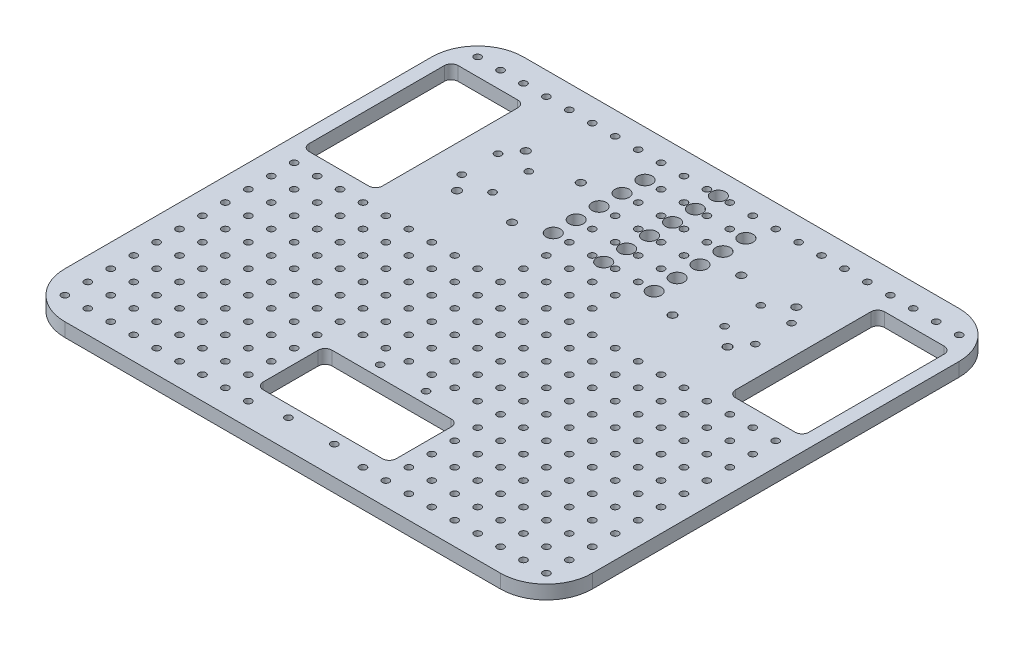
SolidWorks part; units mm, degrees
ref_plane "Спереди" through (0, 0, 0) normal (0, 0, 1) x (1, 0, 0)
ref_plane "Сверху" through (0, 0, 0) normal (0, 1, 0) x (1, 0, 0)
ref_plane "Справа" through (0, 0, 0) normal (1, 0, 0) x (0, 0, -1)
sketch "Эскиз1" plane through (0, 0, 0) normal (0, 1, 0) x (1, 0, 0)
  line L0 (94.4, 150) -> (0, 150) construction
  line L1 (0, 0) -> (230, 0)
  line L6 (115, 0) -> (115, 118.2603) construction
  line L10 (230, 0) -> (230, 200)
  line L28 (230, 200) -> (0, 200)
  line L29 (0, 200) -> (0, 0)
  circle A16 centre (80, 135) radius 1.73
  circle A19 centre (80, 165) radius 1.73
  circle A22 centre (56, 165) radius 1.73
  circle A23 centre (56, 135) radius 1.73
  circle A24 centre (150, 135) radius 1.73
  circle A25 centre (174, 135) radius 1.73
  circle A26 centre (150, 165) radius 1.73
  circle A27 centre (174, 165) radius 1.73
  point P7 (115, 25)
  dimension "D1" = 230
  dimension "D2" = 200
  dimension "D3" = 150
  dimension "D7" = 24
  dimension "D8" = 30
  dimension "D9" = 35
extrude "Бобышка-Вытянуть1" add sketch "Эскиз1" along normal blind 6
fillet "Скругление1" radius 20 4 edges at (0, 3, 0) (230, 3, 0) (230, 3, -200) (0, 3, -200)
sketch "Эскиз2" plane through (0, 6, 0) normal (0, 1, 0) x (1, 0, 0)
  line L0 (174, 165) -> (174, 135) construction
  line L1 (224, 182.5) -> (192, 182.5)
  line L2 (224, 182.5) -> (224, 117.5)
  line L3 (224, 117.5) -> (192, 117.5)
  line L4 (192, 182.5) -> (192, 117.5)
  line L5 (174, 150) -> (192, 150) construction
  line L6 (115, 200) -> (115, 0) construction
  line L7 (210, 200) -> (20, 200) construction
  line L8 (20, 0) -> (210, 0) construction
  line L9 (56, 150) -> (38, 150) construction
  line L10 (56, 165) -> (56, 135) construction
  line L11 (38, 182.5) -> (38, 117.5)
  line L12 (6, 117.5) -> (38, 117.5)
  line L13 (6, 182.5) -> (6, 117.5)
  line L14 (6, 182.5) -> (38, 182.5)
  line L15 (86, 32.5) -> (144, 32.5) construction
  line L16 (86, 47.5) -> (144, 47.5)
  line L17 (86, 47.5) -> (86, 17.5)
  line L18 (86, 17.5) -> (144, 17.5)
  line L19 (144, 47.5) -> (144, 17.5)
  circle A0 centre (105, 12.5) radius 1.5
  circle A1 centre (125, 12.5) radius 1.5
  circle A2 centre (105, 52.5) radius 1.5
  circle A3 centre (125, 52.5) radius 1.5
  dimension "D7" = 3
  dimension "D1" = 65
  dimension "D2" = 18
  dimension "D3" = 32
  dimension "D4" = 58
  dimension "D5" = 30
  dimension "D6" = 17.5
  dimension "D8" = 20
  dimension "D9" = 40
extrude "Вырез-Вытянуть1" cut sketch "Эскиз2" against normal blind 10
fillet "Скругление2" radius 3 12 edges at (224, 3, -117.5) (224, 3, -182.5) (192, 3, -182.5) (192, 3, -117.5) (6, 3, -117.5) (38, 3, -117.5) (38, 3, -182.5) (6, 3, -182.5) (86, 3, -17.5) (144, 3, -17.5) (144, 3, -47.5) (86, 3, -47.5)
sketch "Эскиз3" plane through (0, 6, 0) normal (0, 1, 0) x (1, 0, 0)
  line L0 (20, 0) -> (210, 0) construction
  line L1 (0, 180) -> (0, 20) construction
  line L2 (115, 190) -> (115, 200) construction
  line L3 (210, 200) -> (20, 200) construction
  circle A0 centre (10, 10) radius 1.5
  circle A1 centre (20, 10) radius 1.5
  circle A2 centre (30, 10) radius 1.5
  circle A3 centre (40, 10) radius 1.5
  circle A4 centre (50, 10) radius 1.5
  circle A5 centre (60, 10) radius 1.5
  circle A6 centre (70, 10) radius 1.5
  circle A7 centre (80, 10) radius 1.5
  circle A8 centre (90, 10) radius 1.5
  circle A13 centre (140, 10) radius 1.5
  circle A14 centre (150, 10) radius 1.5
  circle A15 centre (160, 10) radius 1.5
  circle A16 centre (170, 10) radius 1.5
  circle A17 centre (180, 10) radius 1.5
  circle A18 centre (190, 10) radius 1.5
  circle A19 centre (200, 10) radius 1.5
  circle A20 centre (210, 10) radius 1.5
  circle A21 centre (220, 10) radius 1.5
  circle A22 centre (20, 20) radius 1.5
  circle A23 centre (30, 20) radius 1.5
  circle A24 centre (40, 20) radius 1.5
  circle A25 centre (50, 20) radius 1.5
  circle A26 centre (60, 20) radius 1.5
  circle A27 centre (70, 20) radius 1.5
  circle A28 centre (80, 20) radius 1.5
  circle A35 centre (150, 20) radius 1.5
  circle A36 centre (160, 20) radius 1.5
  circle A37 centre (170, 20) radius 1.5
  circle A38 centre (180, 20) radius 1.5
  circle A39 centre (190, 20) radius 1.5
  circle A40 centre (200, 20) radius 1.5
  circle A41 centre (210, 20) radius 1.5
  circle A42 centre (220, 20) radius 1.5
  circle A43 centre (20, 30) radius 1.5
  circle A44 centre (30, 30) radius 1.5
  circle A45 centre (40, 30) radius 1.5
  circle A46 centre (50, 30) radius 1.5
  circle A47 centre (60, 30) radius 1.5
  circle A48 centre (70, 30) radius 1.5
  circle A49 centre (80, 30) radius 1.5
  circle A56 centre (150, 30) radius 1.5
  circle A57 centre (160, 30) radius 1.5
  circle A58 centre (170, 30) radius 1.5
  circle A59 centre (180, 30) radius 1.5
  circle A60 centre (190, 30) radius 1.5
  circle A61 centre (200, 30) radius 1.5
  circle A62 centre (210, 30) radius 1.5
  circle A63 centre (220, 30) radius 1.5
  circle A64 centre (20, 40) radius 1.5
  circle A65 centre (30, 40) radius 1.5
  circle A66 centre (40, 40) radius 1.5
  circle A67 centre (50, 40) radius 1.5
  circle A68 centre (60, 40) radius 1.5
  circle A69 centre (70, 40) radius 1.5
  circle A70 centre (80, 40) radius 1.5
  circle A77 centre (150, 40) radius 1.5
  circle A78 centre (160, 40) radius 1.5
  circle A79 centre (170, 40) radius 1.5
  circle A80 centre (180, 40) radius 1.5
  circle A81 centre (190, 40) radius 1.5
  circle A82 centre (200, 40) radius 1.5
  circle A83 centre (210, 40) radius 1.5
  circle A84 centre (220, 40) radius 1.5
  circle A85 centre (20, 50) radius 1.5
  circle A86 centre (30, 50) radius 1.5
  circle A87 centre (40, 50) radius 1.5
  circle A88 centre (50, 50) radius 1.5
  circle A89 centre (60, 50) radius 1.5
  circle A90 centre (70, 50) radius 1.5
  circle A91 centre (80, 50) radius 1.5
  circle A98 centre (150, 50) radius 1.5
  circle A99 centre (160, 50) radius 1.5
  circle A100 centre (170, 50) radius 1.5
  circle A101 centre (180, 50) radius 1.5
  circle A102 centre (190, 50) radius 1.5
  circle A103 centre (200, 50) radius 1.5
  circle A104 centre (210, 50) radius 1.5
  circle A105 centre (220, 50) radius 1.5
  circle A106 centre (20, 60) radius 1.5
  circle A107 centre (30, 60) radius 1.5
  circle A108 centre (40, 60) radius 1.5
  circle A109 centre (50, 60) radius 1.5
  circle A110 centre (60, 60) radius 1.5
  circle A111 centre (70, 60) radius 1.5
  circle A112 centre (80, 60) radius 1.5
  circle A113 centre (90, 60) radius 1.5
  circle A114 centre (100, 60) radius 1.5
  circle A115 centre (110, 60) radius 1.5
  circle A116 centre (120, 60) radius 1.5
  circle A117 centre (130, 60) radius 1.5
  circle A118 centre (140, 60) radius 1.5
  circle A119 centre (150, 60) radius 1.5
  circle A120 centre (160, 60) radius 1.5
  circle A121 centre (170, 60) radius 1.5
  circle A122 centre (180, 60) radius 1.5
  circle A123 centre (190, 60) radius 1.5
  circle A124 centre (200, 60) radius 1.5
  circle A125 centre (210, 60) radius 1.5
  circle A126 centre (220, 60) radius 1.5
  circle A127 centre (20, 70) radius 1.5
  circle A128 centre (30, 70) radius 1.5
  circle A129 centre (40, 70) radius 1.5
  circle A130 centre (50, 70) radius 1.5
  circle A131 centre (60, 70) radius 1.5
  circle A132 centre (70, 70) radius 1.5
  circle A133 centre (80, 70) radius 1.5
  circle A134 centre (90, 70) radius 1.5
  circle A135 centre (100, 70) radius 1.5
  circle A136 centre (110, 70) radius 1.5
  circle A137 centre (120, 70) radius 1.5
  circle A138 centre (130, 70) radius 1.5
  circle A139 centre (140, 70) radius 1.5
  circle A140 centre (150, 70) radius 1.5
  circle A141 centre (160, 70) radius 1.5
  circle A142 centre (170, 70) radius 1.5
  circle A143 centre (180, 70) radius 1.5
  circle A144 centre (190, 70) radius 1.5
  circle A145 centre (200, 70) radius 1.5
  circle A146 centre (210, 70) radius 1.5
  circle A147 centre (220, 70) radius 1.5
  circle A148 centre (20, 80) radius 1.5
  circle A149 centre (30, 80) radius 1.5
  circle A150 centre (40, 80) radius 1.5
  circle A151 centre (50, 80) radius 1.5
  circle A152 centre (60, 80) radius 1.5
  circle A153 centre (70, 80) radius 1.5
  circle A154 centre (80, 80) radius 1.5
  circle A155 centre (90, 80) radius 1.5
  circle A156 centre (100, 80) radius 1.5
  circle A157 centre (110, 80) radius 1.5
  circle A158 centre (120, 80) radius 1.5
  circle A159 centre (130, 80) radius 1.5
  circle A160 centre (140, 80) radius 1.5
  circle A161 centre (150, 80) radius 1.5
  circle A162 centre (160, 80) radius 1.5
  circle A163 centre (170, 80) radius 1.5
  circle A164 centre (180, 80) radius 1.5
  circle A165 centre (190, 80) radius 1.5
  circle A166 centre (200, 80) radius 1.5
  circle A167 centre (210, 80) radius 1.5
  circle A168 centre (220, 80) radius 1.5
  circle A169 centre (20, 90) radius 1.5
  circle A170 centre (30, 90) radius 1.5
  circle A171 centre (40, 90) radius 1.5
  circle A172 centre (50, 90) radius 1.5
  circle A173 centre (60, 90) radius 1.5
  circle A174 centre (70, 90) radius 1.5
  circle A175 centre (80, 90) radius 1.5
  circle A176 centre (90, 90) radius 1.5
  circle A177 centre (100, 90) radius 1.5
  circle A178 centre (110, 90) radius 1.5
  circle A179 centre (120, 90) radius 1.5
  circle A180 centre (130, 90) radius 1.5
  circle A181 centre (140, 90) radius 1.5
  circle A182 centre (150, 90) radius 1.5
  circle A183 centre (160, 90) radius 1.5
  circle A184 centre (170, 90) radius 1.5
  circle A185 centre (180, 90) radius 1.5
  circle A186 centre (190, 90) radius 1.5
  circle A187 centre (200, 90) radius 1.5
  circle A188 centre (210, 90) radius 1.5
  circle A189 centre (220, 90) radius 1.5
  circle A190 centre (20, 100) radius 1.5
  circle A191 centre (30, 100) radius 1.5
  circle A192 centre (40, 100) radius 1.5
  circle A193 centre (50, 100) radius 1.5
  circle A194 centre (60, 100) radius 1.5
  circle A195 centre (70, 100) radius 1.5
  circle A196 centre (80, 100) radius 1.5
  circle A197 centre (90, 100) radius 1.5
  circle A198 centre (100, 100) radius 1.5
  circle A199 centre (110, 100) radius 1.5
  circle A200 centre (120, 100) radius 1.5
  circle A201 centre (130, 100) radius 1.5
  circle A202 centre (140, 100) radius 1.5
  circle A203 centre (150, 100) radius 1.5
  circle A204 centre (160, 100) radius 1.5
  circle A205 centre (170, 100) radius 1.5
  circle A206 centre (180, 100) radius 1.5
  circle A207 centre (190, 100) radius 1.5
  circle A208 centre (200, 100) radius 1.5
  circle A209 centre (210, 100) radius 1.5
  circle A210 centre (220, 100) radius 1.5
  circle A211 centre (20, 110) radius 1.5
  circle A212 centre (30, 110) radius 1.5
  circle A213 centre (40, 110) radius 1.5
  circle A214 centre (50, 110) radius 1.5
  circle A215 centre (60, 110) radius 1.5
  circle A216 centre (70, 110) radius 1.5
  circle A217 centre (80, 110) radius 1.5
  circle A218 centre (90, 110) radius 1.5
  circle A219 centre (100, 110) radius 1.5
  circle A220 centre (110, 110) radius 1.5
  circle A221 centre (120, 110) radius 1.5
  circle A222 centre (130, 110) radius 1.5
  circle A223 centre (140, 110) radius 1.5
  circle A224 centre (150, 110) radius 1.5
  circle A225 centre (160, 110) radius 1.5
  circle A226 centre (170, 110) radius 1.5
  circle A227 centre (180, 110) radius 1.5
  circle A228 centre (190, 110) radius 1.5
  circle A229 centre (200, 110) radius 1.5
  circle A230 centre (210, 110) radius 1.5
  circle A231 centre (220, 110) radius 1.5
  circle A240 centre (100, 120) radius 1.5
  circle A241 centre (110, 120) radius 1.5
  circle A242 centre (120, 120) radius 1.5
  circle A243 centre (130, 120) radius 1.5
  circle A261 centre (100, 130) radius 1.5
  circle A262 centre (110, 130) radius 1.5
  circle A263 centre (120, 130) radius 1.5
  circle A264 centre (130, 130) radius 1.5
  circle A282 centre (100, 140) radius 1.5
  circle A283 centre (110, 140) radius 1.5
  circle A284 centre (120, 140) radius 1.5
  circle A285 centre (130, 140) radius 1.5
  circle A303 centre (100, 150) radius 1.5
  circle A304 centre (110, 150) radius 1.5
  circle A305 centre (120, 150) radius 1.5
  circle A306 centre (130, 150) radius 1.5
  circle A324 centre (100, 160) radius 1.5
  circle A325 centre (110, 160) radius 1.5
  circle A326 centre (120, 160) radius 1.5
  circle A327 centre (130, 160) radius 1.5
  circle A345 centre (100, 170) radius 1.5
  circle A346 centre (110, 170) radius 1.5
  circle A347 centre (120, 170) radius 1.5
  circle A348 centre (130, 170) radius 1.5
  circle A366 centre (100, 180) radius 1.5
  circle A367 centre (110, 180) radius 1.5
  circle A368 centre (120, 180) radius 1.5
  circle A369 centre (130, 180) radius 1.5
  circle A379 centre (20, 190) radius 1.5
  circle A380 centre (30, 190) radius 1.5
  circle A381 centre (40, 190) radius 1.5
  circle A382 centre (50, 190) radius 1.5
  circle A383 centre (60, 190) radius 1.5
  circle A384 centre (70, 190) radius 1.5
  circle A385 centre (80, 190) radius 1.5
  circle A386 centre (90, 190) radius 1.5
  circle A387 centre (100, 190) radius 1.5
  circle A388 centre (110, 190) radius 1.5
  circle A389 centre (120, 190) radius 1.5
  circle A390 centre (130, 190) radius 1.5
  circle A391 centre (140, 190) radius 1.5
  circle A392 centre (150, 190) radius 1.5
  circle A393 centre (160, 190) radius 1.5
  circle A394 centre (170, 190) radius 1.5
  circle A395 centre (180, 190) radius 1.5
  circle A396 centre (190, 190) radius 1.5
  circle A397 centre (200, 190) radius 1.5
  circle A398 centre (210, 190) radius 1.5
  circle A399 centre (220, 190) radius 1.5
  circle A400 centre (10, 20) radius 1.5
  circle A401 centre (10, 30) radius 1.5
  circle A402 centre (10, 40) radius 1.5
  circle A403 centre (10, 50) radius 1.5
  circle A404 centre (10, 60) radius 1.5
  circle A405 centre (10, 70) radius 1.5
  circle A406 centre (10, 80) radius 1.5
  circle A407 centre (10, 90) radius 1.5
  circle A408 centre (10, 100) radius 1.5
  circle A409 centre (10, 110) radius 1.5
  circle A417 centre (10, 190) radius 1.5
  circle A418 centre (20, 120) radius 1.5 [skipped]
  circle A419 centre (30, 120) radius 1.5 [skipped]
  circle A420 centre (40, 120) radius 1.5 [skipped]
  circle A421 centre (50, 120) radius 1.5 [skipped]
  circle A422 centre (60, 120) radius 1.5 [skipped]
  circle A423 centre (70, 120) radius 1.5 [skipped]
  circle A424 centre (80, 120) radius 1.5 [skipped]
  circle A425 centre (90, 120) radius 1.5 [skipped]
  circle A426 centre (20, 130) radius 1.5 [skipped]
  circle A427 centre (30, 130) radius 1.5 [skipped]
  circle A428 centre (40, 130) radius 1.5 [skipped]
  circle A429 centre (50, 130) radius 1.5 [skipped]
  circle A430 centre (60, 130) radius 1.5 [skipped]
  circle A431 centre (70, 130) radius 1.5 [skipped]
  circle A432 centre (80, 130) radius 1.5 [skipped]
  circle A433 centre (90, 130) radius 1.5 [skipped]
  circle A434 centre (20, 140) radius 1.5 [skipped]
  circle A435 centre (30, 140) radius 1.5 [skipped]
  circle A436 centre (40, 140) radius 1.5 [skipped]
  circle A437 centre (50, 140) radius 1.5 [skipped]
  circle A438 centre (60, 140) radius 1.5 [skipped]
  circle A439 centre (70, 140) radius 1.5 [skipped]
  circle A440 centre (80, 140) radius 1.5 [skipped]
  circle A441 centre (90, 140) radius 1.5 [skipped]
  circle A442 centre (20, 150) radius 1.5 [skipped]
  circle A443 centre (30, 150) radius 1.5 [skipped]
  circle A444 centre (40, 150) radius 1.5 [skipped]
  circle A445 centre (50, 150) radius 1.5 [skipped]
  circle A446 centre (60, 150) radius 1.5 [skipped]
  circle A447 centre (70, 150) radius 1.5 [skipped]
  circle A448 centre (80, 150) radius 1.5 [skipped]
  circle A449 centre (90, 150) radius 1.5 [skipped]
  circle A450 centre (20, 160) radius 1.5 [skipped]
  circle A451 centre (30, 160) radius 1.5 [skipped]
  circle A452 centre (40, 160) radius 1.5 [skipped]
  circle A453 centre (50, 160) radius 1.5 [skipped]
  circle A454 centre (60, 160) radius 1.5 [skipped]
  circle A455 centre (70, 160) radius 1.5 [skipped]
  circle A456 centre (80, 160) radius 1.5 [skipped]
  circle A457 centre (90, 160) radius 1.5 [skipped]
  circle A458 centre (20, 170) radius 1.5 [skipped]
  circle A459 centre (30, 170) radius 1.5 [skipped]
  circle A460 centre (40, 170) radius 1.5 [skipped]
  circle A461 centre (50, 170) radius 1.5 [skipped]
  circle A462 centre (60, 170) radius 1.5 [skipped]
  circle A463 centre (70, 170) radius 1.5 [skipped]
  circle A464 centre (80, 170) radius 1.5 [skipped]
  circle A465 centre (90, 170) radius 1.5 [skipped]
  circle A466 centre (20, 180) radius 1.5 [skipped]
  circle A467 centre (30, 180) radius 1.5 [skipped]
  circle A468 centre (40, 180) radius 1.5 [skipped]
  circle A469 centre (50, 180) radius 1.5 [skipped]
  circle A470 centre (60, 180) radius 1.5 [skipped]
  circle A471 centre (70, 180) radius 1.5 [skipped]
  circle A472 centre (80, 180) radius 1.5 [skipped]
  circle A473 centre (90, 180) radius 1.5 [skipped]
  circle A474 centre (10, 120) radius 1.5 [skipped]
  circle A475 centre (10, 130) radius 1.5 [skipped]
  circle A476 centre (10, 140) radius 1.5 [skipped]
  circle A477 centre (10, 150) radius 1.5 [skipped]
  circle A478 centre (10, 160) radius 1.5 [skipped]
  circle A479 centre (10, 170) radius 1.5 [skipped]
  circle A480 centre (10, 180) radius 1.5 [skipped]
  circle A481 centre (140, 120) radius 1.5 [skipped]
  circle A482 centre (150, 120) radius 1.5 [skipped]
  circle A483 centre (160, 120) radius 1.5 [skipped]
  circle A484 centre (170, 120) radius 1.5 [skipped]
  circle A485 centre (180, 120) radius 1.5 [skipped]
  circle A486 centre (190, 120) radius 1.5 [skipped]
  circle A487 centre (200, 120) radius 1.5 [skipped]
  circle A488 centre (210, 120) radius 1.5 [skipped]
  circle A489 centre (220, 120) radius 1.5 [skipped]
  circle A490 centre (140, 130) radius 1.5 [skipped]
  circle A491 centre (150, 130) radius 1.5 [skipped]
  circle A492 centre (160, 130) radius 1.5 [skipped]
  circle A493 centre (170, 130) radius 1.5 [skipped]
  circle A494 centre (180, 130) radius 1.5 [skipped]
  circle A495 centre (190, 130) radius 1.5 [skipped]
  circle A496 centre (200, 130) radius 1.5 [skipped]
  circle A497 centre (210, 130) radius 1.5 [skipped]
  circle A498 centre (220, 130) radius 1.5 [skipped]
  circle A499 centre (140, 140) radius 1.5 [skipped]
  circle A500 centre (150, 140) radius 1.5 [skipped]
  circle A501 centre (160, 140) radius 1.5 [skipped]
  circle A502 centre (170, 140) radius 1.5 [skipped]
  circle A503 centre (180, 140) radius 1.5 [skipped]
  circle A504 centre (190, 140) radius 1.5 [skipped]
  circle A505 centre (200, 140) radius 1.5 [skipped]
  circle A506 centre (210, 140) radius 1.5 [skipped]
  circle A507 centre (220, 140) radius 1.5 [skipped]
  circle A508 centre (140, 150) radius 1.5 [skipped]
  circle A509 centre (150, 150) radius 1.5 [skipped]
  circle A510 centre (160, 150) radius 1.5 [skipped]
  circle A511 centre (170, 150) radius 1.5 [skipped]
  circle A512 centre (180, 150) radius 1.5 [skipped]
  circle A513 centre (190, 150) radius 1.5 [skipped]
  circle A514 centre (200, 150) radius 1.5 [skipped]
  circle A515 centre (210, 150) radius 1.5 [skipped]
  circle A516 centre (220, 150) radius 1.5 [skipped]
  circle A517 centre (140, 160) radius 1.5 [skipped]
  circle A518 centre (150, 160) radius 1.5 [skipped]
  circle A519 centre (160, 160) radius 1.5 [skipped]
  circle A520 centre (170, 160) radius 1.5 [skipped]
  circle A521 centre (180, 160) radius 1.5 [skipped]
  circle A522 centre (190, 160) radius 1.5 [skipped]
  circle A523 centre (200, 160) radius 1.5 [skipped]
  circle A524 centre (210, 160) radius 1.5 [skipped]
  circle A525 centre (220, 160) radius 1.5 [skipped]
  circle A526 centre (140, 170) radius 1.5 [skipped]
  circle A527 centre (150, 170) radius 1.5 [skipped]
  circle A528 centre (160, 170) radius 1.5 [skipped]
  circle A529 centre (170, 170) radius 1.5 [skipped]
  circle A530 centre (180, 170) radius 1.5 [skipped]
  circle A531 centre (190, 170) radius 1.5 [skipped]
  circle A532 centre (200, 170) radius 1.5 [skipped]
  circle A533 centre (210, 170) radius 1.5 [skipped]
  circle A534 centre (220, 170) radius 1.5 [skipped]
  circle A535 centre (140, 180) radius 1.5 [skipped]
  circle A536 centre (150, 180) radius 1.5 [skipped]
  circle A537 centre (160, 180) radius 1.5 [skipped]
  circle A538 centre (170, 180) radius 1.5 [skipped]
  circle A539 centre (180, 180) radius 1.5 [skipped]
  circle A540 centre (190, 180) radius 1.5 [skipped]
  circle A541 centre (200, 180) radius 1.5 [skipped]
  circle A542 centre (210, 180) radius 1.5 [skipped]
  circle A543 centre (220, 180) radius 1.5 [skipped]
  circle A544 centre (90, 20) radius 1.5 [skipped]
  circle A545 centre (100, 20) radius 1.5 [skipped]
  circle A546 centre (110, 20) radius 1.5 [skipped]
  circle A547 centre (120, 20) radius 1.5 [skipped]
  circle A548 centre (130, 20) radius 1.5 [skipped]
  circle A549 centre (140, 20) radius 1.5 [skipped]
  circle A550 centre (90, 30) radius 1.5 [skipped]
  circle A551 centre (100, 30) radius 1.5 [skipped]
  circle A552 centre (110, 30) radius 1.5 [skipped]
  circle A553 centre (120, 30) radius 1.5 [skipped]
  circle A554 centre (130, 30) radius 1.5 [skipped]
  circle A555 centre (140, 30) radius 1.5 [skipped]
  circle A556 centre (90, 40) radius 1.5 [skipped]
  circle A557 centre (100, 40) radius 1.5 [skipped]
  circle A558 centre (110, 40) radius 1.5 [skipped]
  circle A559 centre (120, 40) radius 1.5 [skipped]
  circle A560 centre (130, 40) radius 1.5 [skipped]
  circle A561 centre (140, 40) radius 1.5 [skipped]
  circle A562 centre (90, 50) radius 1.5 [skipped]
  circle A563 centre (100, 50) radius 1.5 [skipped]
  circle A564 centre (110, 50) radius 1.5 [skipped]
  circle A565 centre (120, 50) radius 1.5 [skipped]
  circle A566 centre (130, 50) radius 1.5 [skipped]
  circle A567 centre (140, 50) radius 1.5 [skipped]
  circle A568 centre (100, 10) radius 1.5 [skipped]
  circle A569 centre (110, 10) radius 1.5 [skipped]
  circle A570 centre (120, 10) radius 1.5 [skipped]
  circle A571 centre (130, 10) radius 1.5 [skipped]
  circle A572 centre (115, 190) radius 3.1
  circle A573 centre (115, 180) radius 3.1
  circle A574 centre (115, 170) radius 3.1
  circle A575 centre (115, 160) radius 3.1
  circle A576 centre (115, 150) radius 3.1
  circle A577 centre (115, 140) radius 3.1
  circle A578 centre (137, 180) radius 3.1
  circle A579 centre (93, 180) radius 3.1
  circle A580 centre (93, 170) radius 3.1
  circle A581 centre (137, 170) radius 3.1
  circle A582 centre (93, 160) radius 3.1
  circle A583 centre (137, 160) radius 3.1
  circle A584 centre (93, 150) radius 3.1
  circle A585 centre (137, 150) radius 3.1
  circle A586 centre (93, 140) radius 3.1
  circle A587 centre (137, 140) radius 3.1
  dimension "D1" = 3
  dimension "D5" = 6.2
  dimension "D2" = 10
  dimension "D3" = 10
  dimension "D6" = 10
  dimension "D4" = 19
  dimension "D7" = 6
  dimension "D8" = 2
  dimension "D9" = 2
  dimension "D10" = 5
extrude "Вырез-Вытянуть2" cut sketch "Эскиз3" against normal blind 10
sketch "Эскиз4" plane through (0, 6, 0) normal (0, 1, 0) x (1, 0, 0)
  line L0 (38, 150) -> (192, 150) construction
  line L1 (38, 120.5) -> (38, 179.5) construction
  line L2 (192, 179.5) -> (192, 120.5) construction
  line L3 (57.7, 150) -> (57.7, 168.4112) construction
  line L4 (115, 150) -> (115, 200) construction
  line L5 (210, 200) -> (20, 200) construction
  circle A0 centre (51, 157.9) radius 1.5
  circle A1 centre (64.4, 157.9) radius 1.5
  circle A2 centre (64.4, 142.1) radius 1.5
  circle A3 centre (51, 142.1) radius 1.5
  circle A4 centre (179, 142.1) radius 1.5
  circle A5 centre (165.6, 142.1) radius 1.5
  circle A6 centre (165.6, 157.9) radius 1.5
  circle A7 centre (179, 157.9) radius 1.5
  point P28 (61.3655, 142.1)
  dimension "D1" = 3
  dimension "D2" = 13.4
  dimension "D3" = 15.8
  dimension "D4" = 13
extrude "Вырез-Вытянуть3" cut sketch "Эскиз4" against normal blind 10
